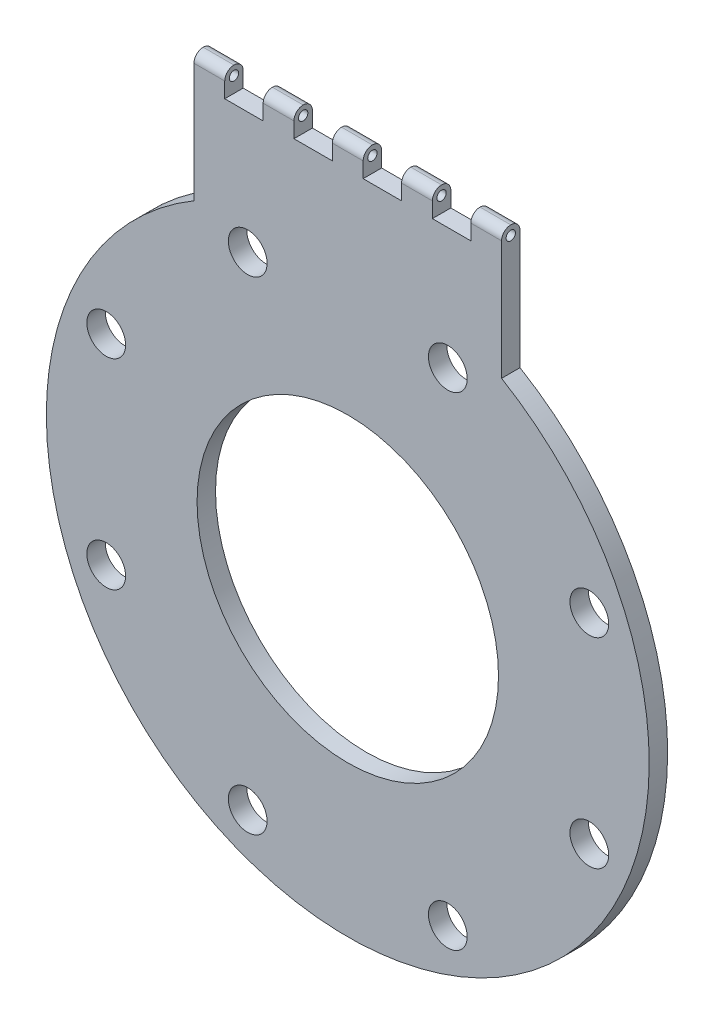
SolidWorks part; units mm, degrees
ref_plane "Front Plane" through (0, 0, 0) normal (0, 0, 1) x (1, 0, 0)
ref_plane "Top Plane" through (0, 0, 0) normal (0, 1, 0) x (1, 0, 0)
ref_plane "Right Plane" through (0, 0, 0) normal (1, 0, 0) x (0, 0, -1)
sketch "Sketch1" plane through (0, 0, 0) normal (0, 0, 1) x (1, 0, 0)
  circle A0 centre (0, 0) radius 49
extrude "Boss-Extrude1" add sketch "Sketch1" along normal blind 3
sketch "Sketch2" plane through (0, 0, 3) normal (0, 0, 1) x (1, 0, 0)
  circle A0 centre (0, 0) radius 24.5
extrude "Cut-Extrude1" cut sketch "Sketch2" against normal blind 3
sketch "Sketch3" plane through (0, 0, 3) normal (0, 0, 1) x (1, 0, 0)
  circle A0 centre (16.264, -39.2649) radius 3.15
  circle A1 centre (39.2649, -16.264) radius 3.15
  circle A2 centre (39.2649, 16.264) radius 3.15
  circle A3 centre (16.264, 39.2649) radius 3.15
  circle A4 centre (-16.264, 39.2649) radius 3.15
  circle A5 centre (-39.2649, 16.264) radius 3.15
  circle A6 centre (-39.2649, -16.264) radius 3.15
  circle A7 centre (-16.264, -39.2649) radius 3.15
  point P0 (0, 0)
extrude "Cut-Extrude2" cut sketch "Sketch3" against normal blind 3
ref_plane "Plane1" through (0, 49, 0) normal (0, 1, 0) x (1, 0, 0)
sketch "Sketch5" plane through (0, 49, 0) normal (0, 1, 0) x (1, 0, 0)
  line L0 (-49, -3) -> (49, -3) construction
  line L1 (-25, 0) -> (25, 0)
  line L2 (-25, 0) -> (-25, -3)
  line L3 (-25, -3) -> (25, -3)
  line L4 (25, 0) -> (25, -3)
  line L5 (-25, 0) -> (25, -3) construction
  line L6 (-25, -3) -> (25, 0) construction
  line L7 (49, 0) -> (-49, 0) construction
  point P0 (0, -1.5)
  dimension "D1" = 0
  dimension "D2" = 50
  dimension "D3" = 0
extrude "Boss-Extrude3" add sketch "Sketch5" along normal blind 10 and the other way up to surface contours L2 L3 L4 L1 other way up to face at (49, 0, 3)
sketch "Sketch6" plane through (0, 59, 0) normal (0, 1, 0) x (1, 0, 0)
  line L0 (-25, -3) -> (25, -3) construction
  line L1 (-25, 0) -> (-20, 0)
  line L2 (-25, 0) -> (-25, -3)
  line L3 (-25, -3) -> (-20, -3)
  line L4 (-20, 0) -> (-20, -3)
  line L5 (-22.5, -3) -> (-22.5, 0) construction
  line L6 (-25, -1.5) -> (-20, -1.5) construction
  point P356 (-22.5, -1.5)
extrude "Boss-Extrude4" add sketch "Sketch6" along normal blind 4
fillet "Fillet1" radius 1.5 2 edges at (-22.5, 63, 0) (-22.5, 63, 3)
sketch "Sketch7" plane through (-25, 0, 0) normal (-1, 0, 0) x (0, 0, 1)
  circle A0 centre (1.5, 61.5) radius 0.7566
  arc A1 (3, 61.5) -> (1.5, 63) centre (1.5, 61.5) ccw construction
  dimension "D1" = 0
pattern_linear "LPattern3" count 5 spacing 11.25 along (1, 0, 0) of "Fillet1", "Boss-Extrude4"
extrude "Cut-Extrude3" cut sketch "Sketch7" against normal through all both and the other way through all
